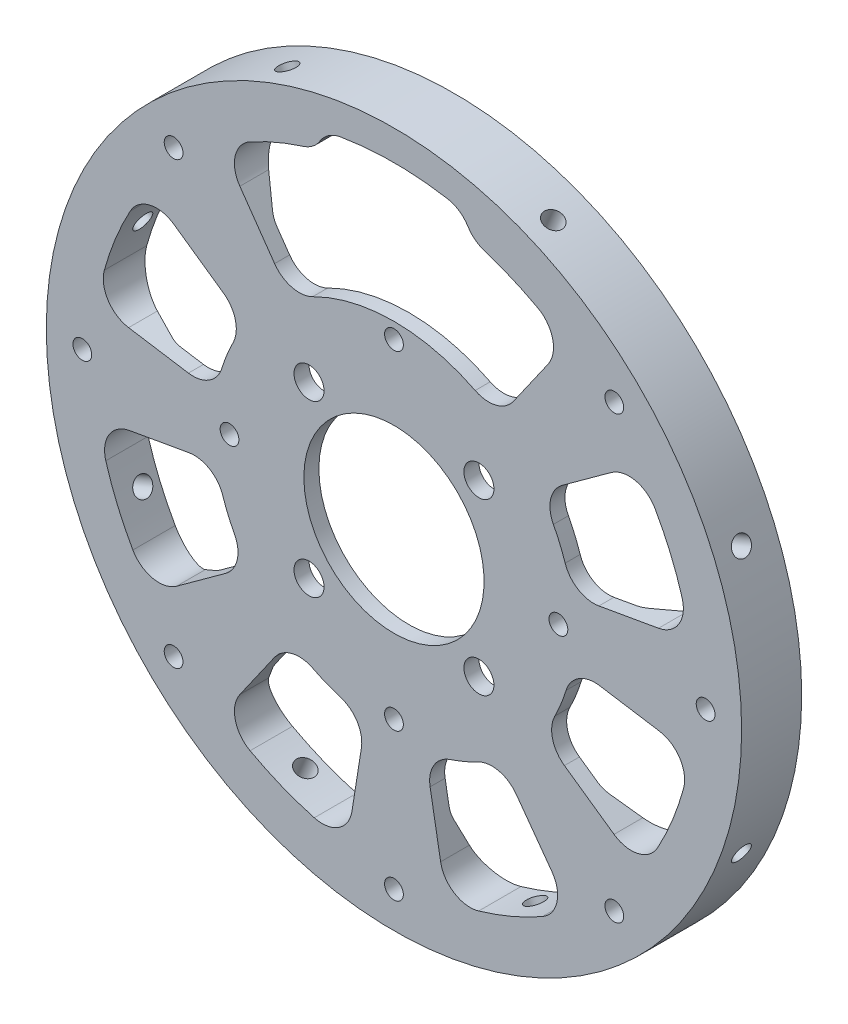
SolidWorks part; units mm, degrees
material "6061 Alloy"
ref_plane "Front Plane" through (0, 0, 0) normal (0, 0, 1) x (1, 0, 0)
ref_plane "Top Plane" through (0, 0, 0) normal (0, 1, 0) x (1, 0, 0)
ref_plane "Right Plane" through (0, 0, 0) normal (1, 0, 0) x (0, 0, -1)
sketch "Sketch6" plane through (0, 0, 0) normal (0, 0, 1) x (1, 0, 0)
  circle A0 centre (0, 0) radius 45.5
  dimension "D1" = 91
extrude "Boss-Extrude1" add sketch "Sketch6" along normal blind 9
sketch "Sketch7" plane through (0, 0, 0) normal (0, 1, 0) x (1, 0, 0)
  line L0 (-45.5, 0) -> (-31.5, -6)
  line L1 (-31.5, -6) -> (0, -6)
  line L2 (0, -6) -> (0, 0)
  line L3 (45.5, 0) -> (-45.5, 0) construction
  line L4 (0, 0) -> (-45.5, 0)
  dimension "D1" = 6
  dimension "D2" = 31.5
revolve "Cut-Revolve1" cut sketch "Sketch7" angle 360 about L2
sketch "Sketch8" plane through (0, 0, 9) normal (0, 0, 1) x (1, 0, 0)
  circle A0 centre (0, 0) radius 45.5
  circle A1 centre (0, 0) radius 46.3
  dimension "D1" = 91
  dimension "D2" = 0.8
extrude "Boss-Extrude2" add sketch "Sketch8" against normal blind 9
sketch "Sketch9" plane through (0, 0, 9) normal (0, 0, 1) x (1, 0, 0)
  line L0 (0, 0) -> (0, 46.3) construction
  line L1 (0, 0) -> (46.3, 0) construction
  line L2 (0, 0) -> (-22.9431, 32.7661) construction
  line L3 (-20.5209, 29.3069) -> (-15.8954, 22.701)
  line L4 (20.5209, 29.3069) -> (15.8954, 22.701)
  circle A0 centre (0, 0) radius 46.3 construction
  arc A1 (-19.1603, 35.1124) -> (19.1603, 35.1124) centre (0, 0) cw
  arc A2 (-10.8161, 21.4246) -> (10.8161, 21.4246) centre (0, 0) cw
  arc A3 (20.5209, 29.3069) -> (19.1603, 35.1124) centre (17.2443, 31.6012) ccw
  arc A4 (15.8954, 22.701) -> (10.8161, 21.4246) centre (12.6188, 24.9953) cw
  arc A5 (-10.8161, 21.4246) -> (-15.8954, 22.701) centre (-12.6188, 24.9953) cw
  arc A6 (-19.1603, 35.1124) -> (-20.5209, 29.3069) centre (-17.2443, 31.6012) ccw
  point P8 (0, 40)
  point P14 (22.9431, 32.7661)
  point P17 (13.7658, 19.6596)
  point P20 (-13.7658, 19.6596)
  dimension "D2" = 40
  dimension "D3" = 24
  dimension "D5" = 4
  dimension "D1" = 90
  dimension "D4" = 35
extrude "Cut-Extrude1" cut sketch "Sketch9" against normal blind 8 and the other way through all
sketch "Sketch10" plane through (0, 0, 9) normal (0, 0, 1) x (1, 0, 0)
  circle A0 centre (0, 0) radius 12
  dimension "D1" = 24
extrude "Cut-Extrude2" cut sketch "Sketch10" against normal blind 8
ref_plane "Plane1" through (-17.7182, 42.7756, 0) normal (-0.3827, 0.9239, 0) x (0, 0, 1)
ref_axis "Axis1" through (0, 0, -0.4) along (0, 0, 1)
ref_plane "Plane5" through (-17.7182, 42.7756, 0) normal (-0.3827, 0.9239, 0) x (0, 0, 1)
sketch "Sketch33" plane through (-17.7182, 42.7756, 0) normal (-0.3827, 0.9239, 0) x (0, 0, 1)
  line L0 (-0.4, 0) -> (8.4, 0) construction
  line L2 (9, 0) -> (0, 0) construction
  line L3 (9, -46.3) -> (9, 46.3) construction
  circle A0 centre (4.5, 0) radius 1.25
  dimension "D1" = 4.5
  dimension "D2" = 2.5
extrude "Cut-Extrude18" cut sketch "Sketch33" against normal blind 10
pattern_circular "CirPattern5" count 8 over 360 about axis through (0, 0, 0) along (0, 0, 1) of "Cut-Extrude18"
sketch "Sketch14" plane through (0, 0, 9) normal (0, 0, 1) x (1, 0, 0)
  line L0 (0, 0) -> (0, 16) construction
  line L1 (0, 0) -> (11.3137, 11.3137) construction
  circle A0 centre (0, 0) radius 16 construction
  circle A1 centre (11.3137, 11.3137) radius 2
  dimension "D1" = 32
  dimension "D3" = 4
  dimension "D2" = 45
extrude "Cut-Extrude6" cut sketch "Sketch14" against normal blind 10
pattern_circular "CirPattern4" count 4 over 360 about axis through (0, 0, 9) along (0, 0, 1) of "Cut-Extrude6"
sketch "Sketch24" plane through (0, 0, 0) normal (0, 1, 0) x (1, 0, 0)
  line L0 (-46.3, -8) -> (-46.3, -9)
  line L2 (-46.3, -9) -> (-30, -9)
  line L3 (-46.3, -9) -> (46.3, -9) construction
  line L4 (-30, -9) -> (-46.3, -8)
  dimension "D1" = 16.3
  dimension "D2" = 1
revolve "Cut-Revolve3" cut sketch "Sketch24" angle 360 about axis through (0, 0, -0.4) along (0, 0, 1)
sketch "Sketch25" plane through (0, 0, 9) normal (0, 0, 1) x (1, 0, 0)
  line L0 (0, 0) -> (0, 46.3) construction
  line L1 (-8.2822, 30.9096) -> (-10.948, 40.8587)
  line L2 (8.2822, 30.9096) -> (10.948, 40.8587)
  circle A0 centre (0, 0) radius 46.3 construction
  arc A1 (-10.948, 40.8587) -> (10.948, 40.8587) centre (0, 0) cw
  arc A2 (-8.2822, 30.9096) -> (8.2822, 30.9096) centre (0, 0) cw
  dimension "D1" = 32
  dimension "D2" = 42.3
  dimension "D3" = 15
extrude "Cut-Extrude11" cut sketch "Sketch25" against normal through all
fillet "Fillet2" radius 4 2 edges at (-10.948, 40.8587, 4.8084) (10.948, 40.8587, 4.8084)
sketch "Sketch29" plane through (0, 0, 0) normal (0, 1, 0) x (1, 0, 0)
  line L1 (-46.3, -8) -> (46.3, -8)
  line L2 (-46.3, -8) -> (-46.3, -23)
  line L3 (-46.3, -23) -> (46.3, -23)
  line L4 (46.3, -8) -> (46.3, -23)
  line L5 (-46.3, -8) -> (46.3, -8) construction
  line L6 (-46.3, 0) -> (-46.3, -8) construction
  dimension "D1" = 15
  dimension "D2" = 92.6
extrude "Cut-Extrude14" cut sketch "Sketch29" against normal through all both and the other way through all
sketch "Sketch35" plane through (0, 0, 8) normal (0, 0, 1) x (1, 0, 0)
  line L1 (-39.5075, 6.2574) -> (-23.7045, 3.7544)
  line L2 (-32.7661, 22.9431) -> (-19.6596, 13.7658)
  line L3 (-20.5209, 29.3069) -> (-15.8954, 22.701) construction
  arc A0 (-31.606, 5.0059) -> (-26.2129, 18.3544) centre (0, 0) cw construction
  arc A1 (-32.7661, 22.9431) -> (-39.5075, 6.2574) centre (0, 0) ccw
  arc A2 (-19.6596, 13.7658) -> (-23.7045, 3.7544) centre (0, 0) ccw
  point P4 (-29.6699, 11.9874)
  dimension "D1" = 40
  dimension "D2" = 24
  dimension "D3" = 20
  dimension "D4" = 26
extrude "Cut-Extrude19" cut sketch "Sketch35" against normal through all
fillet "Fillet3" radius 4 4 edges at (-19.6596, 13.7658, 7) (-23.7045, 3.7544, 7) (-39.5075, 6.2574, 5.1786) (-32.7661, 22.9431, 5.1786)
pattern_circular "CirPattern6" count 8 over 360 about axis through (0, 0, 8) along (0, 0, -1) skipping 1, 2 of "Cut-Extrude19", "Fillet3"
sketch "Sketch36" plane through (0, 0, 8) normal (0, 0, 1) x (1, 0, 0)
  line L0 (0, 46.3) -> (0, 0) construction
  line L1 (0, 0) -> (-46.3, 0) construction
  circle A0 centre (0, 0) radius 46.3 construction
  circle A1 centre (0, 0) radius 41.5 construction
  circle A2 centre (-41.5, 0) radius 1.25
  circle A3 centre (-29.3449, 29.3449) radius 1.25
  circle A4 centre (0, 41.5) radius 1.25 [skipped]
  circle A5 centre (29.3449, 29.3449) radius 1.25
  circle A6 centre (41.5, 0) radius 1.25
  circle A7 centre (29.3449, -29.3449) radius 1.25
  circle A8 centre (0, -41.5) radius 1.25
  circle A9 centre (-29.3449, -29.3449) radius 1.25
  point P27 (0, 0)
  dimension "D1" = 83
  dimension "D2" = 2.5
  dimension "D3" = 8
extrude "Cut-Extrude20" cut sketch "Sketch36" against normal through all
fillet "Fillet4" radius 4 2 edges at (-10.3528, 38.637, 5.1786) (10.3528, 38.637, 5.1786)
fillet "Fillet5" radius 4 7 edges at (22.0786, 22.4674, 6) (31.4988, 0.2749, 6) (22.4674, -22.0786, 6) (0.2749, -31.4988, 6) (-22.0786, -22.4674, 6) (-31.4988, -0.2749, 6) (-22.2739, 22.2739, 6)
sketch "Sketch37" plane through (0, 0, 8) normal (0, 0, 1) x (1, 0, 0)
  circle A0 centre (0, 0) radius 21.9 construction
  circle A1 centre (0, 21.9) radius 1.25
  circle A2 centre (21.9, 0) radius 1.25
  circle A3 centre (0, -21.9) radius 1.25
  circle A4 centre (-21.9, 0) radius 1.25
  point P14 (0, 0)
  dimension "D1" = 43.8
  dimension "D2" = 2.5
  dimension "D3" = 4
extrude "Cut-Extrude21" cut sketch "Sketch37" against normal through all
